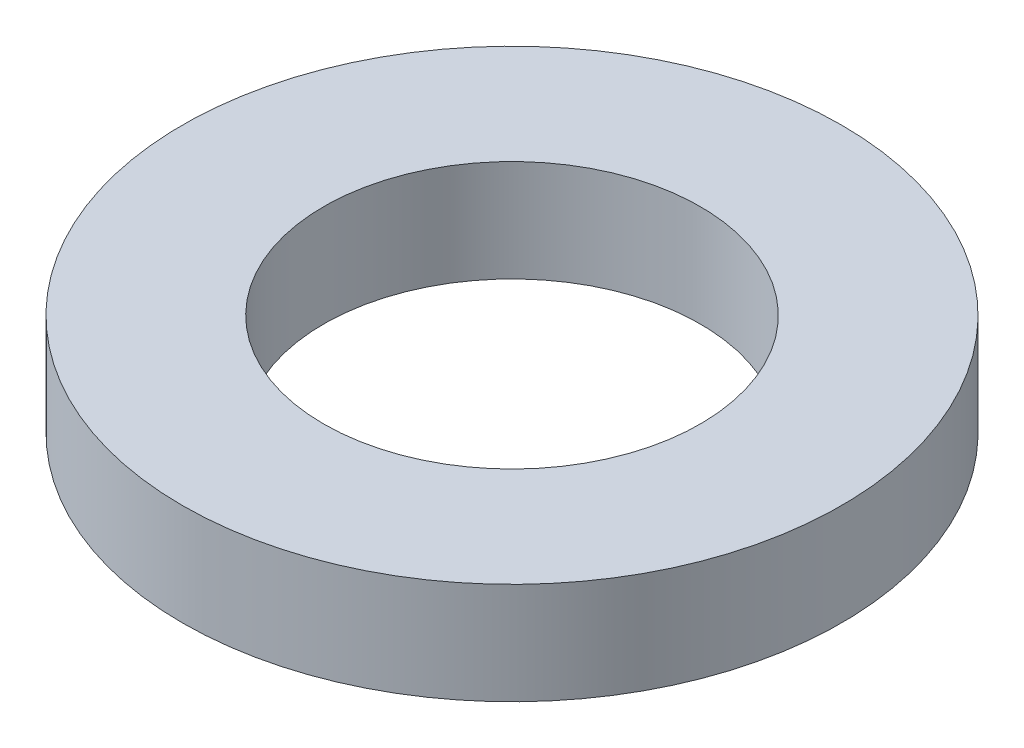
SolidWorks part; units mm, degrees
ref_plane "Front Plane" through (0, 0, 0) normal (0, 0, 1) x (1, 0, 0)
ref_plane "Top Plane" through (0, 0, 0) normal (0, 1, 0) x (1, 0, 0)
ref_plane "Right Plane" through (0, 0, 0) normal (1, 0, 0) x (0, 0, -1)
sketch "Sketch1" plane through (0, 0, 0) normal (0, 1, 0) x (1, 0, 0)
  circle A0 centre (0, 0) radius 87.5
  dimension "FLANGE_OD" = 175
extrude "Boss-Extrude1" add sketch "Sketch1" along normal blind 27
sketch "Sketch2" plane through (0, 0, 0) normal (0, 1, 0) x (1, 0, 0)
  circle A0 centre (0, 0) radius 50
  dimension "BORE_D" = 100
extrude "Cut-Extrude1" cut sketch "Sketch2" along normal through all
sketch "Sketch3" plane through (0, 27, 0) normal (0, 1, 0) x (1, 0, 0)
  circle A0 centre (0, 0) radius 33.4132 construction
  circle A1 centre (-33.4132, 0) radius 6.4772
  dimension "BOLT_D" = 12.9544
  dimension "BOLT_PCD" = 66.8265
extrude "Cut-Extrude2" cut sketch "Sketch3" against normal blind 26.2346 rebuild error yes
pattern_circular "CirPattern1" count 4 over 360 rebuild error yes
